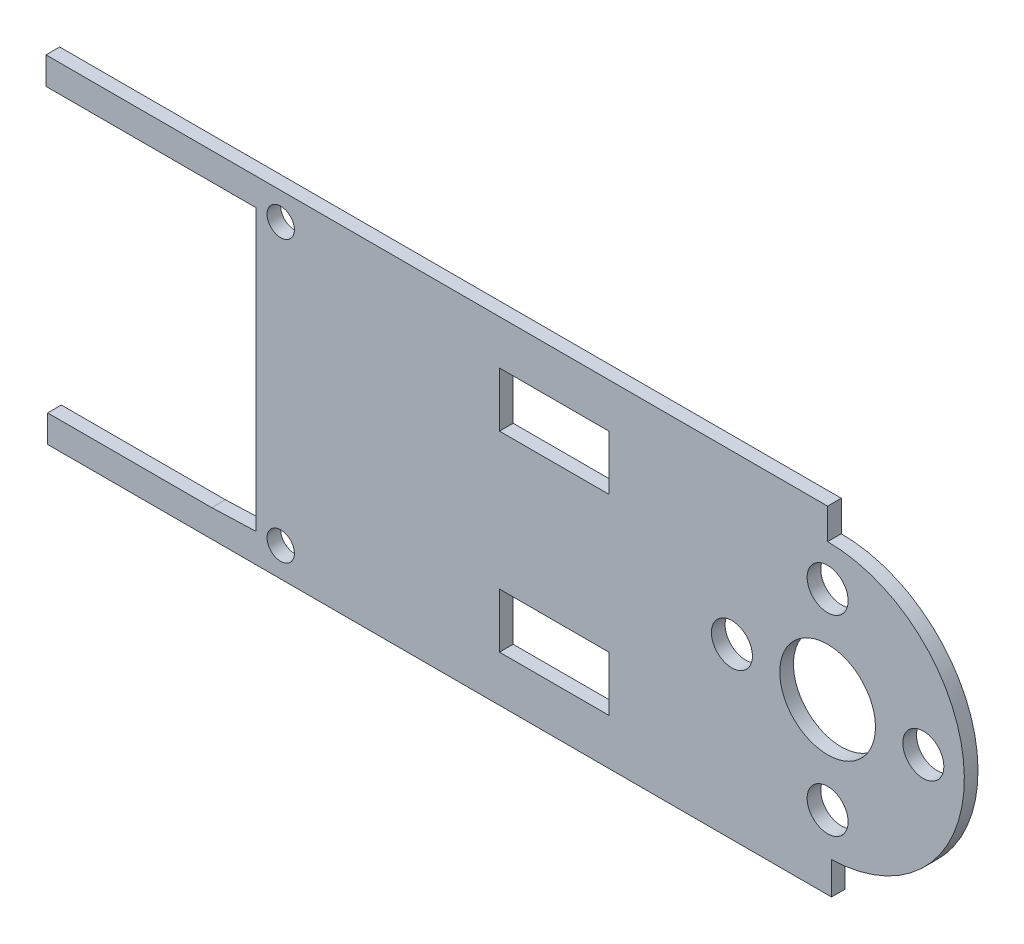
SolidWorks part; units mm, degrees
ref_plane "Front Plane" through (0, 0, 0) normal (0, 0, 1) x (1, 0, 0)
ref_plane "Top Plane" through (0, 0, 0) normal (0, 1, 0) x (1, 0, 0)
ref_plane "Right Plane" through (0, 0, 0) normal (1, 0, 0) x (0, 0, -1)
sketch "Sketch1" plane through (0, 0, 0) normal (0, 0, 1) x (1, 0, 0)
  line L0 (-5.1665, 12.25) -> (-17.1665, 12.25)
  line L1 (-5.1665, 12.25) -> (5, 12.25)
  line L3 (-5.0482, -12.3681) -> (5.2163, -12.3681)
  line L5 (-5.1665, 12.25) -> (5.2163, -12.3681) construction
  line L6 (-5.0482, -12.3681) -> (5, 12.25) construction
  line L7 (-17.1665, 12.25) -> (-17.1665, 10.25)
  line L8 (-17.1665, 10.25) -> (-5.0482, 10.25)
  line L9 (-5.0482, -12.3681) -> (-17.0482, -12.3681)
  line L10 (-17.0482, -12.3681) -> (-17.0482, -10.3681)
  line L11 (-17.0482, -10.3681) -> (-5.0482, -10.3681)
  line L12 (5, 12.25) -> (40, 12.25)
  line L13 (40, 12.25) -> (40, 10)
  line L14 (40.2847, -12.3681) -> (5.2163, -12.3681)
  line L15 (-5.0482, 10.25) -> (-1.7982, 10.25)
  line L16 (40.2847, -9.9959) -> (40.2847, -12.3681)
  line L17 (16, 9) -> (24, 9)
  line L18 (16, 9) -> (16, 5)
  line L19 (16, 5) -> (24, 5)
  line L20 (24, 9) -> (24, 5)
  line L21 (16, 9) -> (24, 5) construction
  line L22 (16, 5) -> (24, 9) construction
  line L23 (16, -5) -> (24, -5)
  line L24 (16, -5) -> (16, -9)
  line L25 (16, -9) -> (24, -9)
  line L26 (24, -5) -> (24, -9)
  line L27 (16, -5) -> (24, -9) construction
  line L28 (16, -9) -> (24, -5) construction
  line L29 (-1.7982, 10.25) -> (-1.7982, -10.25)
  line L30 (-1.7982, -10.25) -> (-5.0482, -10.3681)
  circle A0 centre (0, 10.25) radius 1
  circle A1 centre (0, -10.25) radius 1
  arc A2 (40.2847, -9.9959) -> (40, 10) centre (40, 0) ccw
  circle A3 centre (40, 7) radius 1.5
  circle A4 centre (47, 0) radius 1.5
  circle A5 centre (40, -7) radius 1.5
  circle A6 centre (33, 0) radius 1.5
  circle A7 centre (40, 0) radius 3.5
  point P4 (0, 0)
  point P22 (20, 7)
  point P35 (20, -7)
  dimension "D3" = 2
  dimension "D4" = 2
  dimension "D11" = 20
  dimension "D12" = 3
  dimension "D15" = 7
  dimension "D1" = 20.5
  dimension "D2" = 10.25
  dimension "D5" = 2
  dimension "D6" = 2
  dimension "D7" = 2
  dimension "D8" = 12
  dimension "D9" = 12
  dimension "D10" = 35
  dimension "D13" = 7
  dimension "D16" = 0
  dimension "D17" = 3.25
  dimension "D18" = 3.25
  dimension "D19" = 20
  dimension "D20" = 4
  dimension "D21" = 4
  dimension "D22" = 8
  dimension "D23" = 8
  dimension "D24" = 40
  dimension "D25" = 3.25
  dimension "D14" = 4
extrude "Boss-Extrude1" add sketch "Sketch1" along normal blind 1
sketch "Sketch3" plane through (0, 0, 1) normal (0, 0, 1) x (1, 0, 0)
  line L9 (-17.0482, -12.3681) -> (40.2847, -12.3681)
  line L10 (40.2847, -12.3681) -> (40.2847, -9.9959)
  line L11 (40, 10) -> (40, 12.25)
  line L12 (40, 12.25) -> (-17.1665, 12.25)
  line L13 (-17.1665, 12.25) -> (-17.1665, 10.25)
  line L14 (-17.1665, 10.25) -> (-1.7982, 10.25)
  line L15 (-1.7982, 10.25) -> (-1.7982, -10.25)
  line L16 (-5.0482, -10.3681) -> (-17.0482, -10.3681)
  line L17 (-17.0482, -10.3681) -> (-17.0482, -12.3681)
  line L18 (-17.0482, -12.3681) -> (40.2847, -12.3681)
  line L19 (40.2847, -12.3681) -> (40.2847, -9.9959)
  line L20 (40, 10) -> (40, 12.25)
  line L21 (40, 12.25) -> (-17.1665, 12.25)
  line L22 (-17.1665, 12.25) -> (-17.1665, 10.25)
  line L23 (-17.1665, 10.25) -> (-1.7982, 10.25)
  line L25 (-5.0482, -10.3681) -> (-17.0482, -10.3681)
  line L26 (-17.0482, -10.3681) -> (-17.0482, -12.3681)
  line L28 (-1.7982, 10.25) -> (-1.7982, -10.25)
  line L29 (-1.7982, -10.25) -> (-5.0482, -10.3681)
  line L30 (-1.7982, -10.25) -> (-5.0482, -10.3681)
  arc A1 (40.2847, -9.9959) -> (40, 10) centre (40, 0) ccw
  arc A2 (40.2847, -9.9959) -> (40, 10) centre (40, 0) ccw
  dimension "D1" = 0
